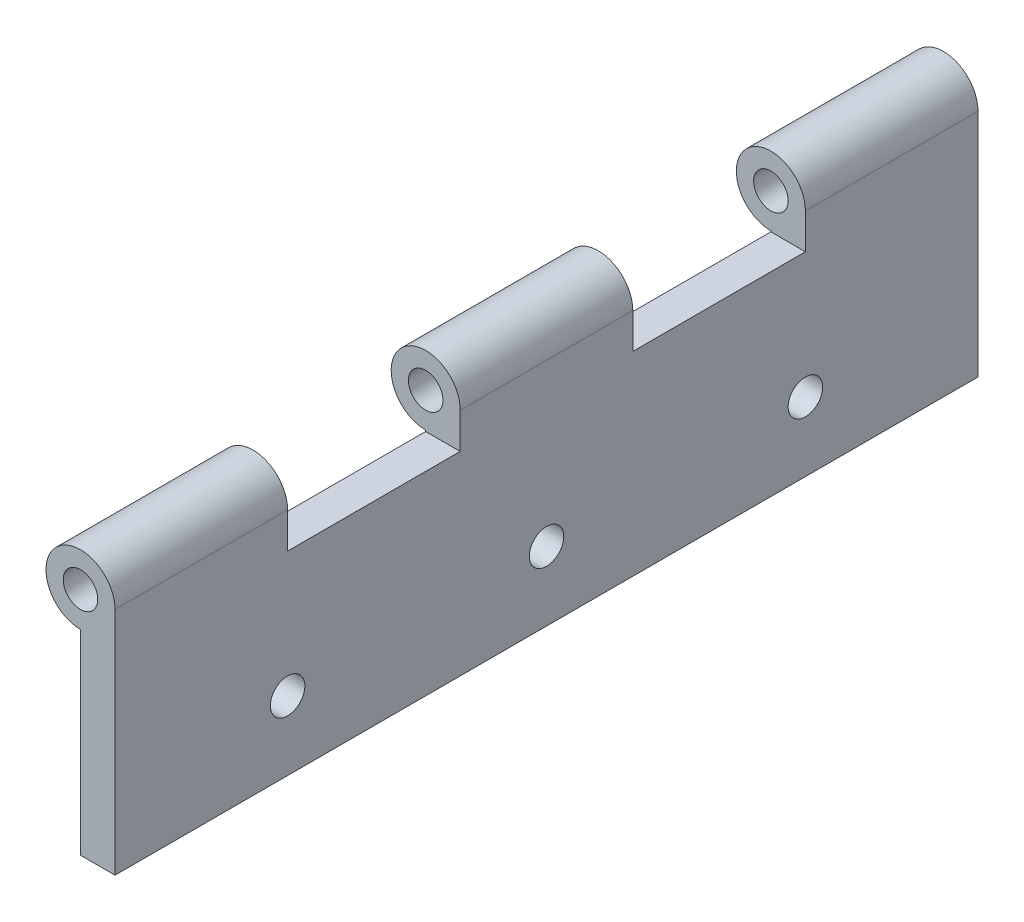
SolidWorks part; units mm, degrees
ref_plane "Front" through (0, 0, 0) normal (0, 0, 1) x (1, 0, 0)
ref_plane "Top" through (0, 0, 0) normal (0, 1, 0) x (1, 0, 0)
ref_plane "Right" through (0, 0, 0) normal (1, 0, 0) x (0, 0, -1)
sketch "Sketch2" plane through (0, 0, 0) normal (0, 0, 1) x (1, 0, 0)
  line L0 (-2.0465, -13.6436) -> (-2.0465, 3.3564)
  line L1 (-2.0465, -13.6436) -> (0.9535, -13.6436)
  line L4 (0.9535, -13.6436) -> (0.9535, 6.3564)
  line L5 (-2.0465, -13.6436) -> (0.9535, 6.3564) construction
  line L6 (-0.6226, 8.909) -> (0.9535, -13.6436) construction
  arc A2 (0.9535, 6.3564) -> (-2.0465, 3.3564) centre (-2.0465, 6.3564) ccw
  circle A3 centre (-2.0465, 6.3564) radius 1.5
  point P0 (0, 0)
  dimension "D3" = 3
  dimension "D1" = 3
  dimension "D2" = 20
extrude "Boss-Extrude1" add sketch "Sketch2" along normal blind 37.5 and the other way blind 37.5
sketch "Sketch4" plane through (-2.0465, 0, 0) normal (-1, 0, 0) x (0, 0, 1)
  line L0 (-37.5, -13.6436) -> (37.5, -13.6436) construction
  line L1 (-22.5, 13.2774) -> (-7.5, 13.2774)
  line L2 (-22.5, 13.2774) -> (-22.5, 3.2774)
  line L3 (-22.5, 3.2774) -> (-7.5, 3.2774)
  line L4 (-7.5, 13.2774) -> (-7.5, 3.2774)
  line L5 (-22.5, 13.2774) -> (-7.5, 3.2774) construction
  line L6 (-22.5, 3.2774) -> (-7.5, 13.2774) construction
  line L7 (7.5, 13.251) -> (22.5, 13.251)
  line L8 (7.5, 13.251) -> (7.5, 3.251)
  line L9 (7.5, 3.251) -> (22.5, 3.251)
  line L10 (22.5, 13.251) -> (22.5, 3.251)
  line L11 (7.5, 13.251) -> (22.5, 3.251) construction
  line L12 (7.5, 3.251) -> (22.5, 13.251) construction
  circle A0 centre (-22.5, -7.6436) radius 1.5
  circle A1 centre (0, -7.6436) radius 1.5
  circle A2 centre (22.5, -7.6436) radius 1.5
  point P0 (-15, 8.2774)
  point P5 (15, 8.251)
  dimension "D7" = 6
  dimension "D1" = 10
  dimension "D2" = 15
  dimension "D3" = 15
  dimension "D4" = 10
  dimension "D5" = 15
  dimension "D6" = 15
  dimension "D8" = 6
  dimension "D9" = 22.5
  dimension "D10" = 22.5
extrude "Cut-Extrude3" cut sketch "Sketch4" against normal blind 10 and the other way blind 10
